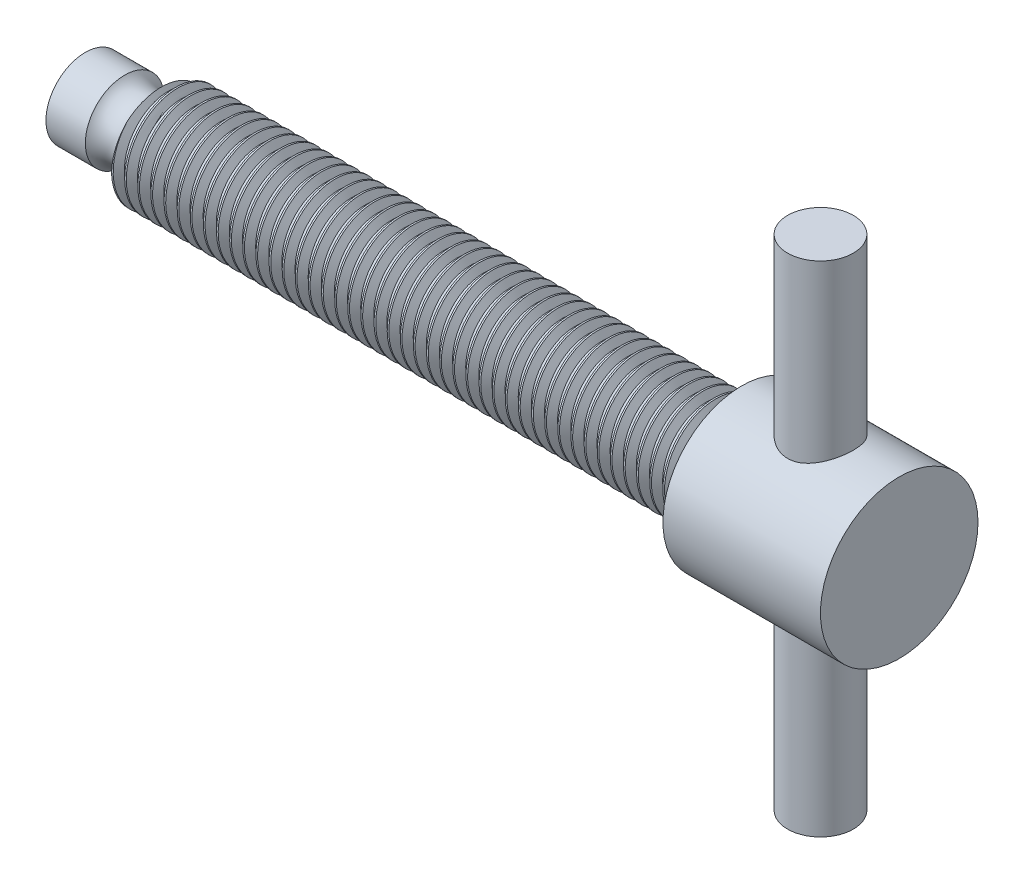
SolidWorks part; units mm, degrees
ref_plane "Front Plane" through (0, 0, 0) normal (0, 0, 1) x (1, 0, 0)
ref_plane "Top Plane" through (0, 0, 0) normal (0, 1, 0) x (1, 0, 0)
ref_plane "Right Plane" through (0, 0, 0) normal (1, 0, 0) x (0, 0, -1)
sketch "Sketch1" plane through (0, 0, 0) normal (0, 1, 0) x (1, 0, 0)
  line L0 (73.2525, 0) -> (-73.2525, 0) construction
  line L1 (0, 6) -> (-12, 6)
  line L2 (-12, 6) -> (-12, 4)
  line L3 (-12, 4) -> (-56, 4)
  line L4 (-59, 3) -> (-62, 3)
  line L5 (-62, 3) -> (-62, 0)
  line L6 (0, 6) -> (0, 0)
  line L7 (-62, 0) -> (0, 0)
  arc A0 (-56, 4) -> (-59, 3) centre (-57.6667, 4) cw
  arc A1 (0, 6) -> (0, -6) centre (-12, 0) cw
  point P4 (0, 0)
  dimension "D4" = 8
  dimension "D1" = 12
  dimension "D2" = 6
  dimension "D3" = 3
  dimension "D5" = 62
  dimension "D6" = 12
  dimension "D7" = 3
  dimension "D8" = 12
revolve "Revolve1" add sketch "Sketch1" angle 360 about L0
sketch "Sketch2" plane through (0, 0, 0) normal (0, 0, 1) x (1, 0, 0)
  line L0 (0, 0) -> (-66.3643, 0) construction
  line L1 (0, -6) -> (0, 6) construction
  line L2 (-8.5, -19) -> (-3.5, -19)
  line L4 (-3.5, -19) -> (-3.5, 19)
  line L5 (-3.5, 19) -> (-8.5, 19)
  line L6 (-8.5, -19) -> (-8.5, 19)
  line L7 (-6, -19) -> (-6, 19)
  point P12 (-8.5, 0)
  dimension "D1" = 38
  dimension "D2" = 6
  dimension "D3" = 5
revolve "Revolve2" add sketch "Sketch2" angle 360 about L7
thread "Thread1" pitch 1 profile "Thread Profile1" start angle 0, offset 1, length 0, pitch 1, diameter 8
ref_plane "Plane1" through (-11, 0, 4) normal (0, -1, 0) x (0, 0, 1)
sketch "Thread Profile1" plane through (-11, 0, 4) normal (0, -1, 0) x (0, 0, 1)
  line L0 (0, 0) -> (0, 1) construction
  line L11 (0, 0) -> (0, 0.875)
  line L12 (0, 0.875) -> (-0.5413, 0.5625)
  line L13 (-0.5413, 0.5625) -> (-0.5413, 0.3125)
  line L15 (-0.5413, 0.3125) -> (0, 0)
  line L17 (-0.5413, 0.4375) -> (0, 0.4375) construction
  point P2 (0, 0)
  dimension "Pitch" = 1
  dimension "Profile_Angle" = 60
  dimension "Profile_Land" = 0.25
  dimension "Profile_Height" = 0.5413
